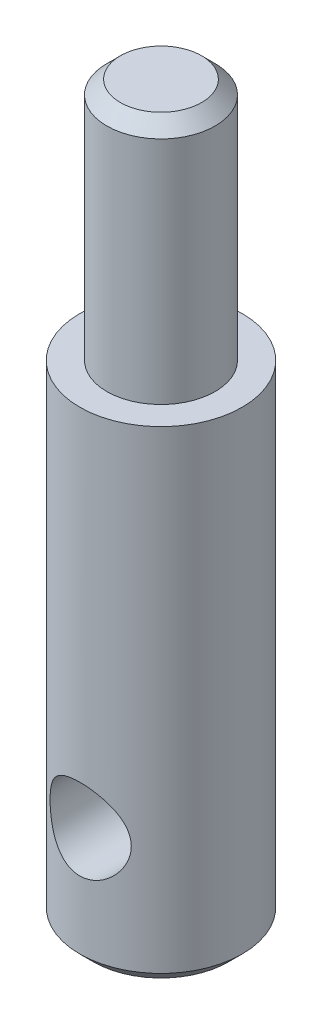
SolidWorks part; units mm, degrees
ref_plane "Front Plane" through (0, 0, 0) normal (0, 0, 1) x (1, 0, 0)
ref_plane "Top Plane" through (0, 0, 0) normal (0, 1, 0) x (1, 0, 0)
ref_plane "Right Plane" through (0, 0, 0) normal (1, 0, 0) x (0, 0, -1)
sketch "Sketch1" plane through (0, 0, 0) normal (0, 1, 0) x (1, 0, 0)
  circle A0 centre (0, 0) radius 4
  circle A1 centre (0, 0) radius 6
extrude "Boss-Extrude1" add sketch "Sketch1" along normal blind 18 contours A0
cosmetic thread "Cosmetic Thread1" parameters "D1"=16, "D2"=6.619
extrude "Boss-Extrude2" add sketch "Sketch1<3>" against normal blind 36 separate body contours A1
sketch "Sketch1<3>" plane through (0, 0, 0) normal (0, 1, 0) x (1, 0, 0) same geometry as "Sketch1"
sketch "Sketch2" plane through (0, 0, 0) normal (0, 0, 1) x (1, 0, 0)
  circle A1 centre (0, -27) radius 3
extrude "Cut-Extrude1" cut sketch "Sketch2" against normal mid plane 36
chamfer "Chamfer1" distance 1 angle 45 1 edges at (0, 18, 4)
chamfer "Chamfer2" distance 1 angle 45 1 edges at (0, -36, 6)
